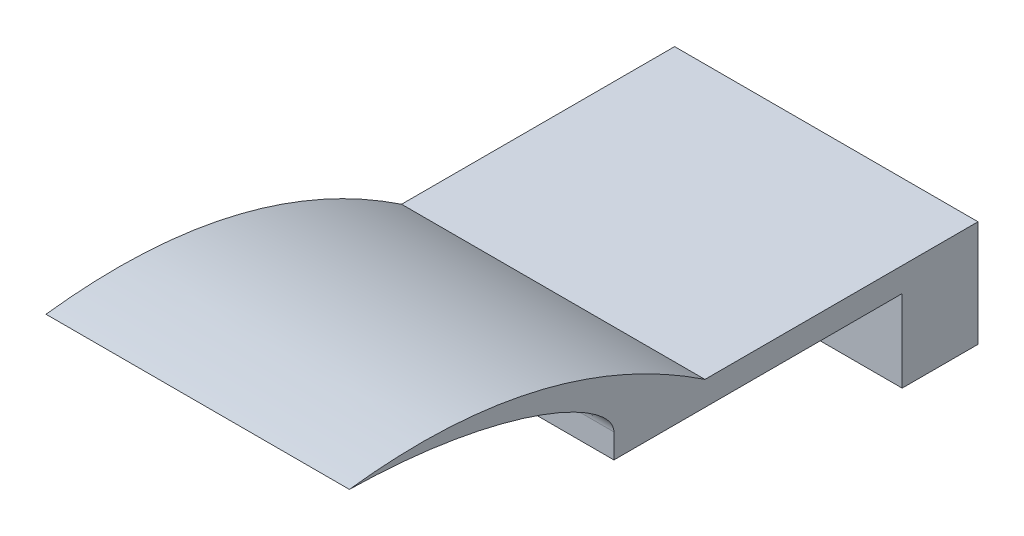
SolidWorks part; units mm, degrees
material "ABS"
ref_plane "Front Plane" through (0, 0, 0) normal (0, 0, 1) x (1, 0, 0)
ref_plane "Top Plane" through (0, 0, 0) normal (0, 1, 0) x (1, 0, 0)
ref_plane "Right Plane" through (0, 0, 0) normal (1, 0, 0) x (0, 0, -1)
curve "Curve1"
  spline degree 3 poles (0, 0.0012, 1.0003) (0, 0.0015, 0.9994) (0, 0.0028, 0.9958) (0, 0.0055, 0.9879) (0, 0.0099, 0.9747) (0, 0.0159, 0.9565) (0, 0.0233, 0.9333) (0, 0.0318, 0.9054) (0, 0.0411, 0.8731) (0, 0.051, 0.8366) (0, 0.0612, 0.7964) (0, 0.0713, 0.7528) (0, 0.0811, 0.7063) (0, 0.0903, 0.6574) (0, 0.0985, 0.6067) (0, 0.1057, 0.5546) (0, 0.1115, 0.5018) (0, 0.1158, 0.4488) (0, 0.1186, 0.3959) (0, 0.1189, 0.3436) (0, 0.1164, 0.2927) (0, 0.1112, 0.2442) (0, 0.1037, 0.1988) (0, 0.0942, 0.157) (0, 0.0831, 0.1194) (0, 0.0711, 0.0865) (0, 0.0584, 0.0585) (0, 0.0457, 0.0357) (0, 0.0334, 0.0184) (0, 0.0218, 0.0064) (0, 0.0108, -0.0005) (0, -0.0003, -0.0011) (0, -0.0092, 0.0055) (0, -0.0148, 0.017) (0, -0.0185, 0.0329) (0, -0.0204, 0.0533) (0, -0.0208, 0.0781) (0, -0.0198, 0.107) (0, -0.0176, 0.1398) (0, -0.0147, 0.176) (0, -0.0111, 0.2153) (0, -0.0074, 0.2574) (0, -0.0037, 0.3019) (0, -0.0005, 0.3484) (0, 0.002, 0.397) (0, 0.0037, 0.4471) (0, 0.0055, 0.4983) (0, 0.0069, 0.5496) (0, 0.0079, 0.6006) (0, 0.0085, 0.6505) (0, 0.0086, 0.699) (0, 0.0083, 0.7455) (0, 0.0076, 0.7894) (0, 0.0065, 0.8302) (0, 0.0053, 0.8675) (0, 0.0039, 0.9007) (0, 0.0027, 0.9296) (0, 0.0013, 0.9539) (0, 0.0006, 0.9727) (0, -0.0011, 0.9872) (0, 0, 0.9944) (0, -0.002, 0.9999) (0, -0.0005, 1) (0, 0, 1) knots 0 0 0 0 0.001372 0.005465 0.012235 0.021602 0.033461 0.047671 0.064081 0.082496 0.102719 0.124527 0.147676 0.171913 0.196978 0.222597 0.248497 0.274385 0.300041 0.32569 0.350525 0.37428 0.396711 0.417577 0.436654 0.453744 0.46868 0.481329 0.491631 0.499616 0.505546 0.510185 0.514824 0.520702 0.528516 0.538466 0.550543 0.564643 0.580638 0.598345 0.617584 0.638174 0.659922 0.682632 0.706121 0.730727 0.7557 0.780732 0.805564 0.829932 0.85357 0.876213 0.89761 0.917519 0.935698 0.951943 0.966047 0.97784 0.987174 0.993932 0.998018 0.999386 1 1 1 1
sketch "Sketch1" plane through (0, 0, 0) normal (1, 0, 0) x (0, 0, -1)
  line L1 (9.9533, 1.5275) -> (9.9533, -8.6325)
  line L3 (48.0533, 1.5275) -> (48.0533, -42.9225)
  line L4 (48.0533, -42.9225) -> (29.0033, -42.9225)
  line L5 (29.0033, -42.9225) -> (29.0033, -8.6325)
  line L6 (29.0033, -8.6325) -> (9.9533, -8.6325)
  line L8 (69.85, 0) -> (-69.85, 0) construction
  line L10 (0, 46.7282) -> (0, -46.7282) construction
  spline S0 degree 2 poles (-100.7907, 36.068) (-19.0327, 46.3014) (48.0533, 1.5275) knots 0 0 0 1 1 1
  spline S1 degree 3 poles (-100.7907, 36.068) (-95.472, 35.9701) (-84.3352, 35.4975) (-67.8427, 33.9153) (-51.8361, 31.4045) (-37.3694, 28.2078) (-24.621, 24.5005) (-13.7375, 20.4579) (-4.8312, 16.2565) (2.0481, 12.0631) (6.8584, 7.9761) (9.4175, 4.4356) (9.9102, 2.2026) (9.9533, 1.5275) knots 0.353791 0.353791 0.353791 0.353791 0.37428 0.396711 0.417577 0.436654 0.453744 0.46868 0.481329 0.491631 0.499616 0.505546 0.508115 0.508115 0.508115 0.508115
  dimension "D2" = 1.5275
  dimension "D3" = 10.16
  dimension "D5" = 100.7907
  dimension "D6" = 38.1
  dimension "D7" = 44.45
  dimension "D8" = 34.29
  dimension "D9" = 19.05
  dimension "D10" = 29.1024
  dimension "D11" = 9.7768
  dimension "D12" = 48.0533
  dimension "D14" = 36.068
extrude "Boss-Extrude1" add sketch "Sketch1" along normal mid plane 127
sketch "Sketch2" plane through (0, 0, -48.0533) normal (0, 0, -1) x (-1, 0, 0)
  line L0 (-63.5, -19.3005) -> (-31.75, -19.3005) construction
  line L1 (-63.5, -42.9225) -> (-63.5, 1.5275) construction
  line L2 (-31.75, -19.3005) -> (31.75, -19.3005) construction
  line L3 (31.75, -19.3005) -> (63.5, -19.3005) construction
  line L4 (63.5, -42.9225) -> (63.5, 1.5275) construction
  line L5 (-63.5, 1.5275) -> (63.5, 1.5275) construction
  circle A0 centre (-31.75, -19.3005) radius 3.175
  circle A1 centre (31.75, -19.3005) radius 3.175
  dimension "D1" = 6.35
  dimension "D2" = 63.5
  dimension "D3" = 20.828
extrude "Cut-Extrude1" cut sketch "Sketch2" against normal through all both and the other way through all
sketch "Sketch3" plane through (0, 0, -48.0533) normal (0, 0, -1) x (-1, 0, 0)
  line L4 (63.5, -42.9225) -> (63.5, 1.5275)
  line L5 (63.5, 1.5275) -> (-63.5, 1.5275)
  line L6 (-63.5, 1.5275) -> (-63.5, -42.9225)
  line L7 (-63.5, -42.9225) -> (63.5, -42.9225)
  line L8 (63.5, -42.9225) -> (63.5, 1.5275)
  line L9 (63.5, 1.5275) -> (-63.5, 1.5275)
  line L10 (-63.5, 1.5275) -> (-63.5, -42.9225)
  line L11 (-63.5, -42.9225) -> (63.5, -42.9225)
  circle A0 centre (-31.75, -19.3005) radius 3.175 construction
  circle A1 centre (-31.75, -19.3005) radius 3.175
  circle A2 centre (31.75, -19.3005) radius 3.175 construction
  circle A3 centre (31.75, -19.3005) radius 3.175
  dimension "D1" = 0
extrude "Boss-Extrude2" add sketch "Sketch3" along normal blind 114.3
sketch "Sketch4" plane through (-63.5, 0, 0) normal (-1, 0, 0) x (0, 0, 1)
  line L0 (-9.9533, -8.6325) -> (-29.0033, -8.6325) construction
  line L1 (-29.0033, -42.9225) -> (-130.6033, -42.9225)
  line L2 (-29.0033, -42.9225) -> (-29.0033, -8.6325)
  line L3 (-29.0033, -8.6325) -> (-130.6033, -8.6325)
  line L4 (-130.6033, -42.9225) -> (-130.6033, -8.6325)
  dimension "D1" = 101.6
extrude "Cut-Extrude2" cut sketch "Sketch4" against normal through all
